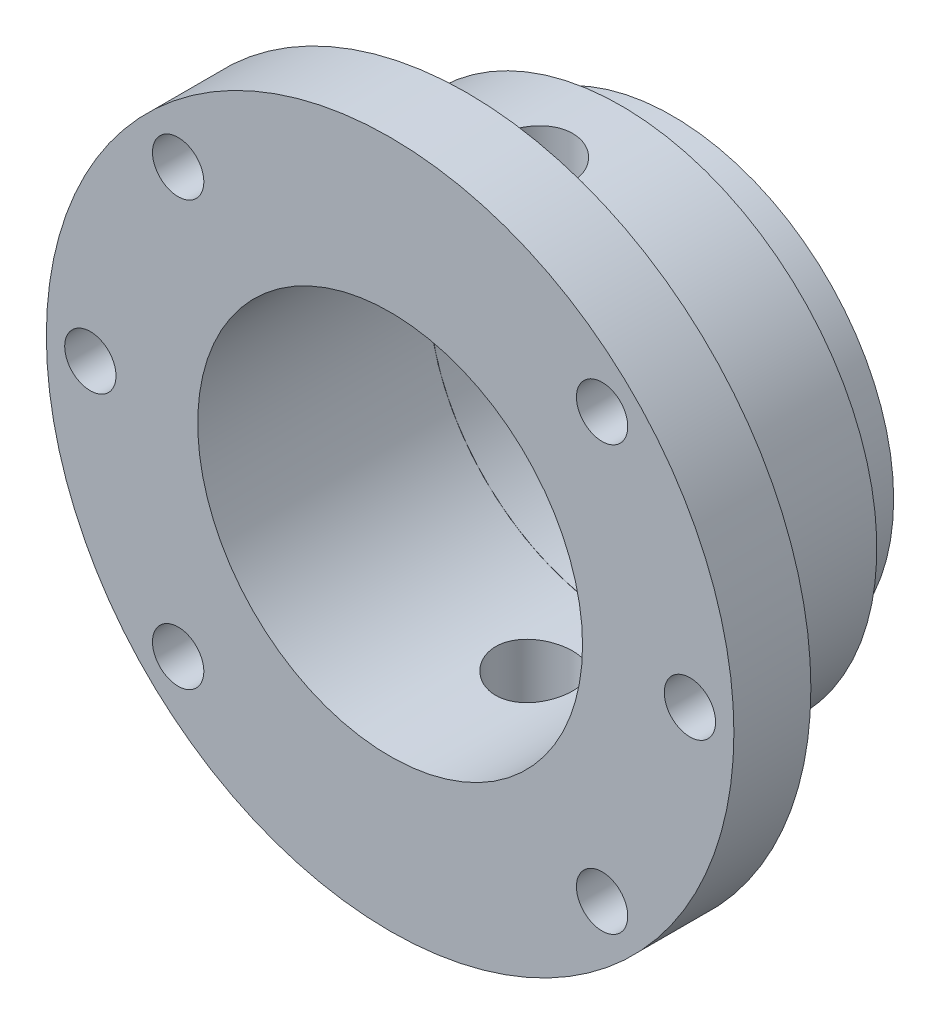
SolidWorks part; units mm, degrees
ref_plane "Спереди" through (0, 0, 0) normal (0, 0, 1) x (1, 0, 0)
ref_plane "Сверху" through (0, 0, 0) normal (0, 1, 0) x (1, 0, 0)
ref_plane "Справа" through (0, 0, 0) normal (1, 0, 0) x (0, 0, -1)
sketch "Эскиз1" plane through (0, 0, 0) normal (0, 0, 1) x (1, 0, 0)
  circle A0 centre (0, 0) radius 15
  circle A1 centre (0, 0) radius 26.8
extrude "Вытянуть1" add sketch "Эскиз1" along normal blind 18
sketch "Эскиз2" plane through (0, 0, 0) normal (0, 0, -1) x (-1, 0, 0)
  circle A0 centre (0, 0) radius 14.9815
  circle A1 centre (0, 0) radius 17.253
extrude "Вытянуть2" add sketch "Эскиз2" along normal blind 4
sketch "Эскиз3" plane through (0, 0, 0) normal (0, 0, -1) x (-1, 0, 0)
  circle A0 centre (0, 0) radius 26.8
  circle A1 centre (0, 0) radius 19.94
extrude "Вытянуть3" cut sketch "Эскиз3" against normal blind 12
sketch "Эскиз5" plane through (0, 0, 12) normal (0, 0, -1) x (-1, 0, 0)
  line L0 (-26.8, 0) -> (-26.8, 18.2105) construction
  circle A0 centre (-23.37, 0) radius 2
  circle A1 centre (-16.5251, 16.5251) radius 2
  circle A3 centre (16.5251, 16.5251) radius 2
  circle A4 centre (23.37, 0) radius 2
  circle A5 centre (16.5251, -16.5251) radius 2
  circle A7 centre (-16.5251, -16.5251) radius 2
  circle A12 centre (0, -23.37) radius 2 [skipped]
  circle A13 centre (0, 23.37) radius 2 [skipped]
  dimension "D1" = 3.43
extrude "Вытянуть4" cut sketch "Эскиз5" against normal through all
sketch "Эскиз6" plane through (0, 0, 12) normal (0, 0, -1) x (-1, 0, 0)
  line L0 (0, 29.0501) -> (0, -2.8906) construction
ref_plane "Плоскость1" through (0, 29.0501, 12) normal (0, -1, 0) x (1, 0, 0)
sketch "Эскиз7" plane through (0, 29.0501, 12) normal (0, -1, 0) x (1, 0, 0)
  circle A0 centre (0, -5.2335) radius 3
extrude "Вытянуть8" cut sketch "Эскиз7" along normal blind 100
